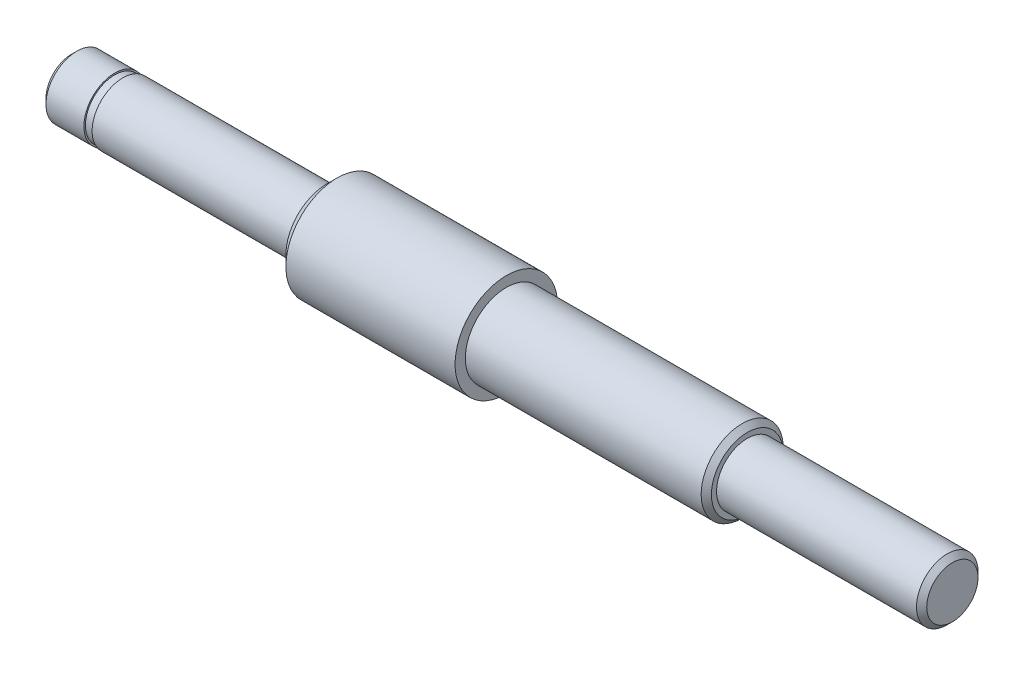
SolidWorks part; units mm, degrees
ref_plane "Alzado" through (0, 0, 0) normal (1, 0, 0) x (0, 1, 0)
ref_plane "Planta" through (0, 0, 0) normal (0, 0, 1) x (0, 1, 0)
ref_plane "Vista lateral" through (0, 0, 0) normal (0, 1, 0) x (-1, 0, 0)
sketch "Croquis1" plane through (0, 0, 0) normal (0, 1, 0) x (-1, 0, 0)
  line L0 (-42.95, 0) -> (-42.95, 3)
  line L1 (-42.95, 3) -> (-22.95, 3)
  line L2 (-22.95, 3) -> (-22.95, 4)
  line L3 (-22.95, 4) -> (0.55, 4)
  line L6 (42.95, 3) -> (42.95, 0)
  line L7 (-42.95, 0) -> (42.95, 0) construction
  line L9 (37.95, 3) -> (37.95, 2.85)
  line L10 (37.95, 2.85) -> (38.75, 2.85)
  line L11 (38.75, 2.85) -> (38.75, 3)
  line L12 (38.75, 3) -> (42.95, 3)
  line L14 (0.55, 4) -> (0.55, 5)
  line L15 (0.55, 5) -> (18.05, 5)
  line L16 (18.05, 5) -> (18.05, 3)
  line L17 (18.05, 3) -> (37.95, 3)
  line L19 (-42.95, 0) -> (42.95, 0)
  point P6 (42.95, 1.5)
  dimension "D2" = 6
  dimension "D4" = 8
  dimension "D8" = 0.8
  dimension "D1" = 20
  dimension "D9" = 19.9
  dimension "D12" = 10
  dimension "D10" = 43.5
  dimension "D5" = 5
  dimension "D3" = 17.5
  dimension "D6" = 5.7
revolve "Revolución1" add sketch "Croquis1" angle 360 about L7
chamfer "Chaflán1" distance 0.5 angle 45 3 edges at (-42.95, 0, -3) (42.95, 0, -3) (22.95, 0, -4)
chamfer "Chaflán2" distance 1 angle 45 1 edges at (-18.05, 0, -5)
equation "\"ancho_circlip\"=0.8"
equation "\"D8@Croquis1\"=\"ancho_circlip\""
equation "\"ranura_circlip\"=0.45"
equation "\"d_circlip\"=5.7"
equation "\"D6@Croquis1\"=\"d_circlip\""
